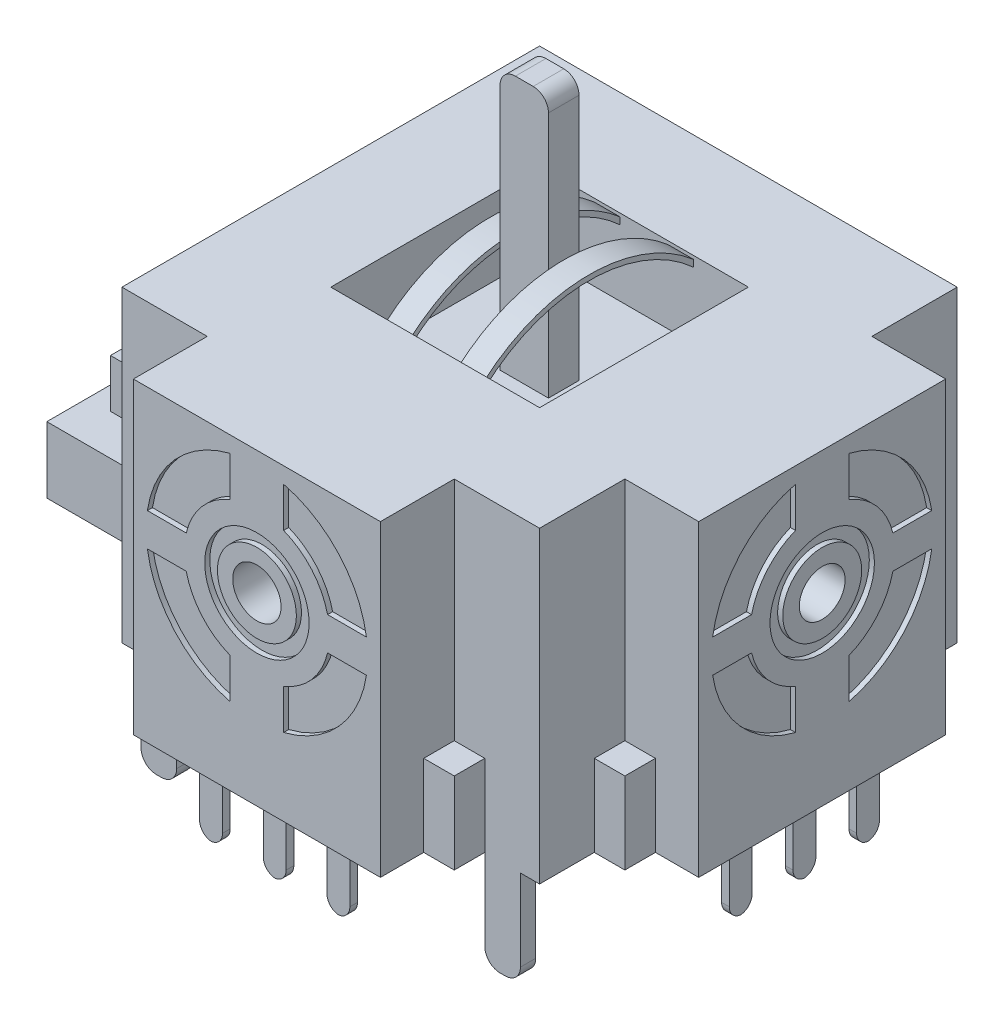
SolidWorks part; units mm, degrees
ref_plane "前视基准面" through (0, 0, 0) normal (0, 0, 1) x (1, 0, 0)
ref_plane "上视基准面" through (0, 0, 0) normal (0, 1, 0) x (1, 0, 0)
ref_plane "右视基准面" through (0, 0, 0) normal (1, 0, 0) x (0, 0, -1)
other "Configuration Table"
sketch "草图1" plane through (0, 0, 0) normal (0, 1, 0) x (1, 0, 0)
  line L0 (8.2, 8.2) -> (11.1, 4.85)
  line L1 (-8.2, -8.2) -> (8.2, -8.2)
  line L2 (-8.2, -8.2) -> (-8.2, 8.2)
  line L3 (-8.2, 8.2) -> (8.2, 8.2)
  line L4 (8.2, -8.2) -> (8.2, 8.2)
  line L5 (-8.2, -8.2) -> (8.2, 8.2) construction
  line L6 (-8.2, 8.2) -> (8.2, -8.2) construction
  line L7 (8.2, 4.85) -> (11.1, 4.85)
  line L8 (8.2, 4.85) -> (8.2, -4.85)
  line L9 (8.2, -4.85) -> (11.1, -4.85)
  line L10 (11.1, 4.85) -> (11.1, -4.85)
  line L11 (-4.85, -8.2) -> (4.85, -8.2)
  line L12 (-4.85, -8.2) -> (-4.85, -11.1)
  line L13 (-4.85, -11.1) -> (4.85, -11.1)
  line L14 (4.85, -8.2) -> (4.85, -11.1)
  line L15 (11.1, -4.85) -> (8.2, -8.2)
  line L16 (8.2, -8.2) -> (4.85, -11.1)
  line L17 (-4.85, -11.1) -> (-8.2, -8.2)
  line L18 (-8.2, 8.2) -> (-14.6, 4.75)
  line L19 (-8.2, 4.75) -> (-14.6, 4.75)
  line L20 (-8.2, 4.75) -> (-8.2, -4.75)
  line L21 (-8.2, -4.75) -> (-14.6, -4.75)
  line L22 (-14.6, 4.75) -> (-14.6, -4.75)
  line L23 (-14.6, -4.75) -> (-8.2, -8.2)
  line L24 (-13.7, 3.15) -> (-8.2, 4.75)
  line L25 (-8.2, 3.15) -> (-13.7, 3.15)
  line L26 (-8.2, 3.15) -> (-8.2, -3.15)
  line L27 (-8.2, -3.15) -> (-13.7, -3.15)
  line L28 (-13.7, 3.15) -> (-13.7, -3.15)
  line L29 (-13.7, -3.15) -> (-8.2, -4.75)
  point P0 (0, 0)
  point P10 (11.1, 0)
  dimension "D1" = 16.4
  dimension "D2" = 16.4
  dimension "D3" = 19.3
  dimension "D4" = 19.3
  dimension "D5" = 9.7
  dimension "D6" = 9.7
  dimension "D7" = 25.7
  dimension "D8" = 9.5
  dimension "D9" = 6.3
  dimension "D10" = 24.8
extrude "凸台-拉伸1" add sketch "草图1" against normal blind 12.1 contours L1 L4 L3 L2 | L10 L7 L4 L9 | L14 L1 L12 L13 region at (0, 0, 0) region at (9.65, 0, 0) region at (0, 0, 9.65)
extrude "凸台-拉伸2" add sketch "草图1<3>" along normal blind 2.6 from surface contours L29 L28 L24 L19 L22 L21 | L25 L20 L24 | L25 L28 L27 L20 | L27 L29 L2 region at (-10.982, 0, -4.06) region at (-10.0333, 0, -3.6833) region at (-10.95, 0, 0) region at (-10.0333, 0, 3.6833) starting at face at (3.2167, -12.1, 3.2167)
sketch "草图1<3>" plane through (0, 0, 0) normal (0, 1, 0) x (1, 0, 0) same geometry as "草图1"
extrude "凸台-拉伸3" add sketch "草图1<4>" along normal blind 4.5 from surface contours L25 L28 L27 L20 region at (-10.95, 0, 0) starting at face at (-0.4375, -12.1, 2.4125)
sketch "草图1<4>" plane through (0, 0, 0) normal (0, 1, 0) x (1, 0, 0) same geometry as "草图1"
sketch "草图2" plane through (0, -7.6, 0) normal (0, 1, 0) x (1, 0, 0)
  line L0 (-8.2, 3.15) -> (-13.7, 3.15) construction
  line L1 (-12.9, 2) -> (-13.7, 3.15)
  line L2 (-12.9, -2) -> (-13.7, -3.15)
  line L3 (-13.7, 3.15) -> (-13.7, -3.15) construction
  circle A0 centre (-10.95, 0) radius 1.75
  circle A1 centre (-12.9, 2) radius 0.65
  circle A2 centre (-12.9, -2) radius 0.65
  point P6 (-10.95, 3.15)
  point P10 (-12.7113, 2)
  dimension "D1" = 3.5
  dimension "D2" = 1.3
  dimension "D3" = 4
  dimension "D4" = 0.8
extrude "凸台-拉伸4" add sketch "草图2" along normal blind 5.9 from surface contours A0 starting at face at (-0.4375, -12.1, 2.4125)
extrude "凸台-拉伸5" add sketch "草图2<3>" along normal blind 0.2 contours A1 | A2
sketch "草图2<3>" plane through (0, -7.6, 0) normal (0, 1, 0) x (1, 0, 0) same geometry as "草图2"
sketch "草图3" plane through (0, -12.1, 0) normal (0, -1, 0) x (1, 0, 0)
  line L0 (-8.2, -8.2) -> (8.2, -8.2) construction
  line L1 (-4.85, 8.2) -> (-6.05, 8.2)
  line L2 (-4.85, 8.2) -> (-4.85, 9.4)
  line L3 (-4.85, 9.4) -> (-6.05, 9.4)
  line L4 (-6.05, 8.2) -> (-6.05, 9.4)
  line L5 (4.85, 8.2) -> (6.05, 8.2)
  line L6 (4.85, 8.2) -> (4.85, 9.4)
  line L7 (4.85, 9.4) -> (6.05, 9.4)
  line L8 (6.05, 8.2) -> (6.05, 9.4)
  line L9 (8.2, 4.85) -> (9.4, 4.85)
  line L10 (8.2, 4.85) -> (8.2, 6.05)
  line L11 (8.2, 6.05) -> (9.4, 6.05)
  line L12 (9.4, 4.85) -> (9.4, 6.05)
  line L13 (8.2, -4.85) -> (9.4, -4.85)
  line L14 (8.2, -4.85) -> (8.2, -6.05)
  line L15 (8.2, -6.05) -> (9.4, -6.05)
  line L16 (9.4, -4.85) -> (9.4, -6.05)
  line L17 (4.85, -8.2) -> (6.05, -8.2)
  line L18 (4.85, -8.2) -> (4.85, -9.4)
  line L19 (4.85, -9.4) -> (6.05, -9.4)
  line L20 (6.05, -8.2) -> (6.05, -9.4)
  line L22 (-4.85, -8.2) -> (-6.05, -8.2)
  line L23 (-4.85, -8.2) -> (-4.85, -9.4)
  line L24 (-4.85, -9.4) -> (-6.05, -9.4)
  line L25 (-6.05, -8.2) -> (-6.05, -9.4)
  line L26 (-8.2, 4.75) -> (-9.4, 4.75)
  line L27 (-8.2, 4.75) -> (-8.2, 5.95)
  line L28 (-8.2, 5.95) -> (-9.4, 5.95)
  line L29 (-9.4, 4.75) -> (-9.4, 5.95)
  line L30 (-8.2, -4.75) -> (-9.4, -4.75)
  line L31 (-8.2, -4.75) -> (-8.2, -5.95)
  line L32 (-8.2, -5.95) -> (-9.4, -5.95)
  line L33 (-9.4, -4.75) -> (-9.4, -5.95)
  dimension "D1" = 1.2
extrude "凸台-拉伸6" add sketch "草图3" against normal blind 3.2
sketch "草图5" plane through (0, -12.1, 0) normal (0, -1, 0) x (1, 0, 0)
  line L0 (-8.2, 8.2) -> (-6.05, 8.2) construction
  line L1 (-7.45, 8.2) -> (-6.05, 8.2)
  line L2 (-7.45, 8.2) -> (-7.45, 7.6)
  line L3 (-7.45, 7.6) -> (-6.05, 7.6)
  line L4 (-6.05, 8.2) -> (-6.05, 7.6)
  line L5 (6.05, 8.2) -> (8.2, 8.2) construction
  line L6 (7.45, 8.2) -> (6.05, 8.2)
  line L7 (7.45, 8.2) -> (7.45, 7.6)
  line L8 (7.45, 7.6) -> (6.05, 7.6)
  line L9 (6.05, 8.2) -> (6.05, 7.6)
  line L10 (6.05, -8.2) -> (8.2, -8.2) construction
  line L11 (7.45, -8.2) -> (6.05, -8.2)
  line L12 (7.45, -8.2) -> (7.45, -7.6)
  line L13 (7.45, -7.6) -> (6.05, -7.6)
  line L14 (6.05, -8.2) -> (6.05, -7.6)
  line L15 (-8.2, -8.2) -> (-6.05, -8.2) construction
  line L16 (-7.45, -8.2) -> (-6.05, -8.2)
  line L17 (-7.45, -8.2) -> (-7.45, -7.6)
  line L18 (-7.45, -7.6) -> (-6.05, -7.6)
  line L19 (-6.05, -8.2) -> (-6.05, -7.6)
  line L20 (-6.05, 9.4) -> (-6.05, 8.2) construction
  line L21 (-2.95, 10.4) -> (-2.05, 10.4)
  line L22 (-2.95, 10.4) -> (-2.95, 10.1)
  line L23 (-2.95, 10.1) -> (-2.05, 10.1)
  line L24 (-2.05, 10.4) -> (-2.05, 10.1)
  line L25 (-0.45, 10.4) -> (0.45, 10.4)
  line L26 (-0.45, 10.4) -> (-0.45, 10.1)
  line L27 (-0.45, 10.1) -> (0.45, 10.1)
  line L28 (0.45, 10.4) -> (0.45, 10.1)
  line L29 (2.05, 10.4) -> (2.95, 10.4)
  line L30 (2.05, 10.4) -> (2.05, 10.1)
  line L31 (2.05, 10.1) -> (2.95, 10.1)
  line L32 (2.95, 10.4) -> (2.95, 10.1)
  line L33 (-13.1, 3.25) -> (-12.2, 3.25)
  line L34 (-13.1, 3.25) -> (-13.1, 2.95)
  line L35 (-13.1, 2.95) -> (-12.2, 2.95)
  line L36 (-12.2, 3.25) -> (-12.2, 2.95)
  line L37 (-8.1, 3.25) -> (-7.2, 3.25)
  line L38 (-8.1, 3.25) -> (-8.1, 2.95)
  line L39 (-8.1, 2.95) -> (-7.2, 2.95)
  line L40 (-7.2, 3.25) -> (-7.2, 2.95)
  line L41 (-13.1, -2.95) -> (-12.2, -2.95)
  line L42 (-13.1, -2.95) -> (-13.1, -3.25)
  line L43 (-13.1, -3.25) -> (-12.2, -3.25)
  line L44 (-12.2, -2.95) -> (-12.2, -3.25)
  line L45 (-8.1, -2.95) -> (-7.2, -2.95)
  line L46 (-8.1, -2.95) -> (-8.1, -3.25)
  line L47 (-8.1, -3.25) -> (-7.2, -3.25)
  line L48 (-7.2, -2.95) -> (-7.2, -3.25)
  line L49 (10.4, 2.95) -> (10.1, 2.95)
  line L50 (10.4, 2.95) -> (10.4, 2.05)
  line L51 (10.4, 2.05) -> (10.1, 2.05)
  line L52 (10.1, 2.95) -> (10.1, 2.05)
  line L53 (10.4, 0.45) -> (10.1, 0.45)
  line L54 (10.4, 0.45) -> (10.4, -0.45)
  line L55 (10.4, -0.45) -> (10.1, -0.45)
  line L56 (10.1, 0.45) -> (10.1, -0.45)
  line L57 (10.4, -2.05) -> (10.1, -2.05)
  line L58 (10.4, -2.05) -> (10.4, -2.95)
  line L59 (10.4, -2.95) -> (10.1, -2.95)
  line L60 (10.1, -2.05) -> (10.1, -2.95)
  line L61 (6.05, -9.4) -> (6.05, -8.2) construction
  line L62 (-14.6, -4.75) -> (-14.6, 4.75) construction
  line L63 (-9.4, 4.75) -> (-14.6, 4.75) construction
  line L64 (-9.4, -4.75) -> (-14.6, -4.75) construction
  line L67 (-2.95, 10.4) -> (-4.85, 11.1)
  line L68 (-2.95, 10.1) -> (-4.85, 9.4)
  line L69 (2.95, 10.4) -> (4.85, 11.1)
  line L71 (11.1, 4.85) -> (10.4, 2.95)
  line L72 (10.1, 2.95) -> (9.4, 4.85)
  line L73 (11.1, -4.85) -> (10.4, -2.95)
  dimension "D1" = 1.4
  dimension "D2" = 0.6
  dimension "D3" = 0.9
  dimension "D4" = 0.3
  dimension "D5" = 1.5
  dimension "D6" = 1.5
  dimension "D7" = 1.5
  dimension "D8" = 4.1
  dimension "D9" = 1.6
  dimension "D10" = 1.6
  dimension "D11" = 1.6
  dimension "D12" = 1.6
extrude "凸台-拉伸7" add sketch "草图5" along normal blind 3.8 contours L1 L4 L3 L2 | L18 L19 L16 L17 | L13 L14 L11 L12 | L6 L9 L8 L7
extrude "凸台-拉伸8" add sketch "草图5<3>" along normal blind 2.8 contours L24 L21 L22 L23 | L32 L29 L30 L31 | L57 L60 L59 L58 | L49 L52 L51 L50 | L35 L36 L33 L34 | L43 L44 L41 L42 | L47 L48 L45 L46 | L39 L40 L37 L38 | L25 L28 L27 L26 | L56 L55 L54 L53 region at (-2.5, -12.1, 10.25) region at (2.5, -12.1, 10.25) region at (10.25, -12.1, 2.5) region at (10.25, -12.1, -2.5)
sketch "草图5<3>" plane through (0, -12.1, 0) normal (0, -1, 0) x (1, 0, 0) same geometry as "草图5"
sketch "草图4" plane through (0, 0, 11.1) normal (0, 0, 1) x (1, 0, 0)
  line L0 (-4.85, 0) -> (4.85, 0) construction
  line L1 (4.85, -8.9) -> (4.85, 0) construction
  line L2 (-4.85, -8.9) -> (-4.85, 0) construction
  line L4 (-1.05, -9.0714) -> (1.05, -9.0714)
  line L5 (-1.05, -9.0714) -> (-1.05, -0.6286)
  line L6 (-1.05, -0.6286) -> (1.05, -0.6286)
  line L7 (1.05, -9.0714) -> (1.05, -0.6286)
  line L8 (-1.05, -9.0714) -> (1.05, -0.6286) construction
  line L9 (-1.05, -0.6286) -> (1.05, -9.0714) construction
  line L10 (-4.3012, -5.5) -> (4.3012, -5.5)
  line L11 (-4.3012, -5.5) -> (-4.3012, -4.2)
  line L12 (-4.3012, -4.2) -> (4.3012, -4.2)
  line L13 (4.3012, -5.5) -> (4.3012, -4.2)
  line L14 (-4.3012, -5.5) -> (4.3012, -4.2) construction
  line L15 (-4.3012, -4.2) -> (4.3012, -5.5) construction
  circle A0 centre (0, -4.85) radius 4.85
  circle A1 centre (0, -4.85) radius 4.35
  circle A2 centre (0, -4.85) radius 2.85
  circle A3 centre (0, -4.85) radius 2.05
  circle A4 centre (0, -4.85) radius 1.55
  circle A5 centre (0, -4.85) radius 0.95
  dimension "D1" = 0.5
  dimension "D2" = 1.5
  dimension "D3" = 0.8
  dimension "D4" = 0.5
  dimension "D7" = 1.9
  dimension "D5" = 1.3
  dimension "D6" = 2.1
extrude "切除-拉伸1" cut sketch "草图4" against normal blind 0.2 contours A2 L5 A1 L12 | A2 L10 A1 L5 | A2 L12 A1 L7 | A2 L7 A1 L10 | A3 | A4 region at (-2.6032, -7.1765, 11.1) region at (2.6032, -7.1765, 11.1) region at (-2.6032, -2.5235, 11.1) region at (2.6032, -2.5235, 11.1)
extrude "切除-拉伸2" cut sketch "草图4<3>" against normal through all contours A5
sketch "草图4<3>" plane through (0, 0, 11.1) normal (0, 0, 1) x (1, 0, 0) same geometry as "草图4"
sketch "草图6" plane through (11.1, 0, 0) normal (1, 0, 0) x (0, 0, -1)
  line L0 (4.85, 0) -> (-4.85, 0) construction
  line L1 (-4.85, -12.1) -> (-4.85, 0) construction
  line L2 (4.85, -12.1) -> (4.85, 0) construction
  line L4 (-1.05, -9.7) -> (1.05, -9.7)
  line L5 (-1.05, -9.7) -> (-1.05, 0)
  line L6 (-1.05, 0) -> (1.05, 0)
  line L7 (1.05, -9.7) -> (1.05, 0)
  line L8 (-1.05, -9.7) -> (1.05, 0) construction
  line L9 (-1.05, 0) -> (1.05, -9.7) construction
  line L10 (-4.85, -5.5) -> (4.85, -5.5)
  line L11 (-4.85, -5.5) -> (-4.85, -4.2)
  line L12 (-4.85, -4.2) -> (4.85, -4.2)
  line L13 (4.85, -5.5) -> (4.85, -4.2)
  line L14 (-4.85, -5.5) -> (4.85, -4.2) construction
  line L15 (-4.85, -4.2) -> (4.85, -5.5) construction
  circle A0 centre (0, -4.85) radius 4.85
  circle A1 centre (0, -4.85) radius 4.35
  circle A2 centre (0, -4.85) radius 2.85
  circle A3 centre (0, -4.85) radius 2.05
  circle A4 centre (0, -4.85) radius 1.55
  circle A5 centre (0, -4.85) radius 0.9
  dimension "D1" = 0.5
  dimension "D2" = 1.5
  dimension "D3" = 0.8
  dimension "D4" = 0.5
  dimension "D7" = 1.8
  dimension "D5" = 2.1
  dimension "D6" = 1.3
extrude "切除-拉伸3" cut sketch "草图6" against normal blind 0.2 contours A2 L5 A1 L12 | A2 L12 A1 L7 | A2 L10 A1 L5 | A2 L7 A1 L10 | A3 | A4 region at (11.1, -7.1765, 2.6032) region at (11.1, -7.1765, -2.6032) region at (11.1, -2.5235, 2.6032) region at (11.1, -2.5235, -2.6032)
extrude "切除-拉伸4" cut sketch "草图6<3>" against normal through all contours A5
sketch "草图6<3>" plane through (11.1, 0, 0) normal (1, 0, 0) x (0, 0, -1) same geometry as "草图6"
sketch "草图7" plane through (-8.2, 0, 0) normal (-1, 0, 0) x (0, 0, 1)
  circle A0 centre (0, -4.85) radius 1.3
  dimension "D1" = 2.6
extrude "凸台-拉伸9" add sketch "草图7" along normal blind 3.5
sketch "草图8" plane through (0, 0, 0) normal (0, 1, 0) x (1, 0, 0)
  line L1 (-4.1, -4.1) -> (4.1, -4.1)
  line L2 (-4.1, -4.1) -> (-4.1, 4.1)
  line L3 (-4.1, 4.1) -> (4.1, 4.1)
  line L4 (4.1, -4.1) -> (4.1, 4.1)
  line L5 (-4.1, -4.1) -> (4.1, 4.1) construction
  line L6 (-4.1, 4.1) -> (4.1, -4.1) construction
  line L7 (-0.95, -0.6) -> (0.95, -0.6)
  line L8 (-0.95, -0.6) -> (-0.95, 0.6)
  line L9 (-0.95, 0.6) -> (0.95, 0.6)
  line L10 (0.95, -0.6) -> (0.95, 0.6)
  line L11 (-0.95, -0.6) -> (0.95, 0.6) construction
  line L12 (-0.95, 0.6) -> (0.95, -0.6) construction
  point P0 (0, 0)
  point P5 (0, 0)
  dimension "D1" = 8.2
  dimension "D2" = 1.9
  dimension "D3" = 1.2
extrude "切除-拉伸5" cut sketch "草图8" against normal blind 3 contours L1 L4 L3 L2 | L7 L10 L9 L8
extrude "凸台-拉伸10" add sketch "草图8<2>" along normal blind 7.3 contours L7 L10 L9 L8
sketch "草图8<2>" plane through (0, 0, 0) normal (0, 1, 0) x (1, 0, 0) same geometry as "草图8"
sketch "草图9" plane through (0, 0, 0) normal (1, 0, 0) x (0, 0, -1)
  line L1 (-11.9049, 1.2) -> (12.261, 1.2) construction
  line L2 (4.85, 0) -> (-4.85, 0) construction
  circle A0 centre (0, -4.85) radius 6.05
  dimension "D1" = 1.2
extrude "拉伸-薄壁2" add sketch "草图9" along normal blind 1 from surface thin starting at face at (0.95, 2.15, 0) thin type one direction wall 0.2
extrude "拉伸-薄壁3" add sketch "草图9<3>" against normal blind 1 from surface thin starting at face at (-0.95, 2.15, 0) thin type one direction wall 0.2
sketch "草图9<3>" plane through (0, 0, 0) normal (1, 0, 0) x (0, 0, -1) same geometry as "草图9"
fillet "圆角1" radius 0.5 20 edges at (-13.1, -14.9, -3.1) (-12.2, -14.9, -3.1) (-8.1, -14.9, -3.1) (-7.2, -14.9, -3.1) (-13.1, -14.9, 3.1) (-12.2, -14.9, 3.1) (-8.1, -14.9, 3.1) (-7.2, -14.9, 3.1) (-2.95, -14.9, 10.25) (-2.05, -14.9, 10.25) (-0.45, -14.9, 10.25) (0.45, -14.9, 10.25) (2.05, -14.9, 10.25) (2.95, -14.9, 10.25) (10.25, -14.9, 2.95) (10.25, -14.9, 2.05) (10.25, -14.9, -2.95) (10.25, -14.9, -2.05) (10.25, -14.9, -0.45) (10.25, -14.9, 0.45)
fillet "圆角2" radius 0.6 8 edges at (6.05, -15.9, -7.9) (7.45, -15.9, -7.9) (-7.45, -15.9, -7.9) (-6.05, -15.9, -7.9) (-7.45, -15.9, 7.9) (-6.05, -15.9, 7.9) (6.05, -15.9, 7.9) (7.45, -15.9, 7.9)
fillet "圆角3" radius 0.6 2 edges at (-0.95, 7.3, 0) (0.95, 7.3, 0)
